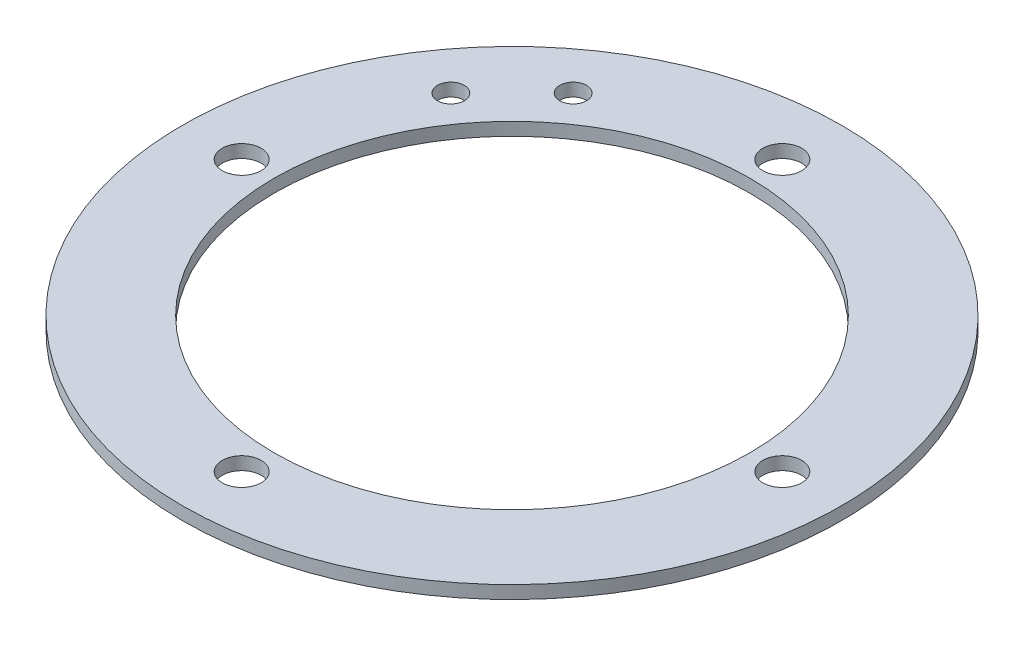
SolidWorks part; units mm, degrees
ref_plane "Front Plane" through (0, 0, 0) normal (0, 0, 1) x (1, 0, 0)
ref_plane "Top Plane" through (0, 0, 0) normal (0, 1, 0) x (1, 0, 0)
ref_plane "Right Plane" through (0, 0, 0) normal (1, 0, 0) x (0, 0, -1)
sketch "Sketch1" plane through (0, 0, 0) normal (0, 1, 0) x (1, 0, 0)
  line L0 (0, 76.2) -> (0, 62.5) construction
  line L1 (0, 62.5) -> (0, 55) construction
  circle A0 centre (0, 0) radius 76.2
  circle A1 centre (0, 0) radius 62.5 construction
  circle A2 centre (0, 62.5) radius 4.5
  circle A3 centre (62.5, 0) radius 4.5
  circle A4 centre (0, -62.5) radius 4.5
  circle A5 centre (-62.5, 0) radius 4.5
  circle A6 centre (0, 0) radius 55
  point P15 (0, 0)
  dimension "D1" = 152.4
  dimension "D2" = 125
  dimension "D3" = 9
  dimension "D5" = 7.5
  dimension "D4" = 4
extrude "Boss-Extrude1" add sketch "Sketch1" along normal blind 3
sketch "Sketch2" plane through (0, 3, 0) normal (0, 1, 0) x (1, 0, 0)
  line L0 (-51.6188, 37.4767) -> (-37.4767, 51.6188) construction
  line L1 (-44.5477, 44.5477) -> (0, 0) construction
  line L2 (-76.2, 0) -> (0, 0) construction
  circle A0 centre (-51.6188, 37.4767) radius 3.1
  circle A1 centre (-37.4767, 51.6188) radius 3.1
  circle A2 centre (0, 0) radius 76.2 construction
  dimension "D3" = 6.2
  dimension "D1" = 20
  dimension "D2" = 45
  dimension "D4" = 63
extrude "Cut-Extrude1" cut sketch "Sketch2" against normal blind 3
